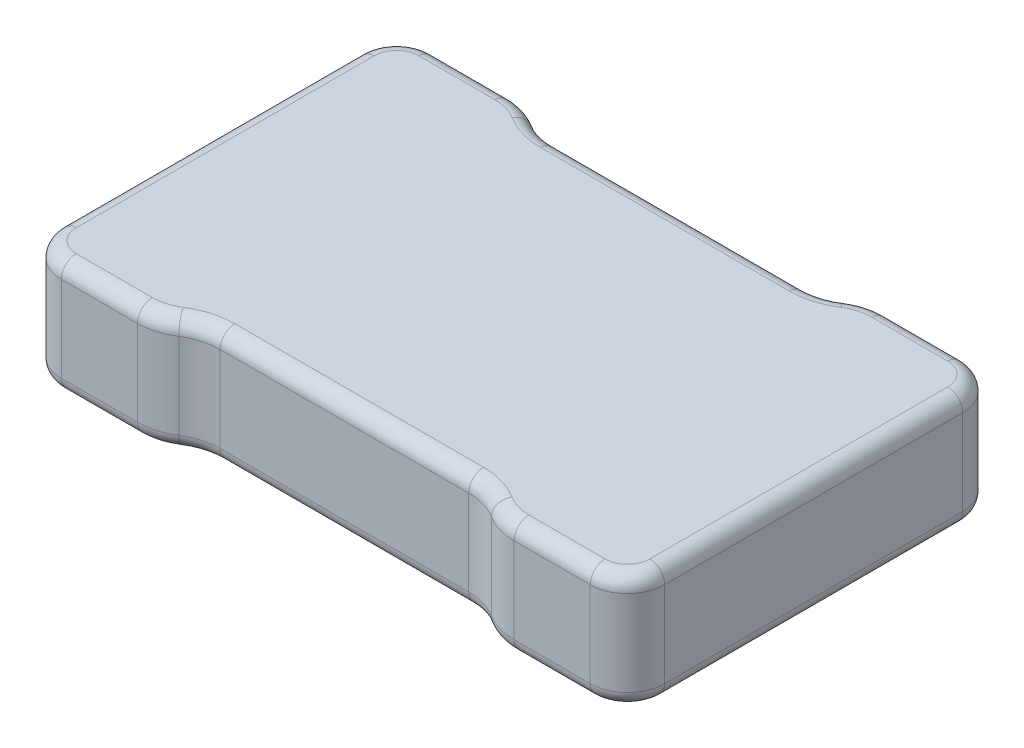
SolidWorks part; units mm, degrees
ref_plane "Front Plane" through (0, 0, 0) normal (0, 0, 1) x (1, 0, 0)
ref_plane "Top Plane" through (0, 0, 0) normal (0, 1, 0) x (1, 0, 0)
ref_plane "Right Plane" through (0, 0, 0) normal (1, 0, 0) x (0, 0, -1)
sketch "Sketch1" plane through (0, 0, 0) normal (0, 1, 0) x (1, 0, 0)
  line L0 (-55, 0) -> (55, 0) construction
  line L1 (-40.5, 25) -> (40.5, 25)
  line L2 (-40.5, 25) -> (-40.5, -25)
  line L3 (-40.5, -25) -> (40.5, -25)
  line L4 (40.5, 25) -> (40.5, -25)
  line L5 (0, -55) -> (0, 55) construction
  dimension "D1" = 25
  dimension "D2" = 50
  dimension "D3" = 81
  dimension "D4" = 40.5
extrude "Boss-Extrude1" add sketch "Sketch1" along normal blind 15.5
sketch "Sketch2" plane through (0, 15.5, 0) normal (0, 1, 0) x (1, 0, 0)
  line L0 (-40.5, 25) -> (-40.5, -25) construction
  line L1 (-40.5, 25) -> (-40.5, 22.5) construction
  line L2 (-40.5, 22.5) -> (-40.5, -22.5) construction
  line L3 (-40.5, -22.5) -> (-40.5, -25) construction
  line L4 (-40.5, 22.5) -> (40.5, 22.5) construction
  line L5 (40.5, -25) -> (40.5, 25) construction
  line L6 (-40.5, -22.5) -> (40.5, -22.5) construction
  line L7 (40.5, 22.5) -> (22.5, 22.5) construction
  line L8 (22.5, 22.5) -> (-22.5, 22.5) construction
  line L9 (-22.5, 22.5) -> (-40.5, 22.5) construction
  line L10 (-22.5, 22.5) -> (-22.5, -25) construction
  line L11 (-40.5, -25) -> (40.5, -25) construction
  line L12 (22.5, 22.5) -> (22.5, -25) construction
  line L13 (22.5, 25) -> (-22.5, 25)
  line L14 (40.5, 25) -> (-40.5, 25) construction
  line L15 (-22.5, 25) -> (-22.5, 22.5)
  line L16 (-22.5, 22.5) -> (22.5, 22.5)
  line L17 (22.5, 22.5) -> (22.5, 25)
  line L18 (-22.5, -25) -> (-22.5, -22.5)
  line L19 (-22.5, -22.5) -> (22.5, -22.5)
  line L20 (22.5, -22.5) -> (22.5, -25)
  line L21 (22.5, -25) -> (-22.5, -25)
  dimension "D1" = 2.5
  dimension "D2" = 2.5
  dimension "D3" = 18
  dimension "D4" = 18
extrude "Cut-Extrude1" cut sketch "Sketch2" against normal through all
fillet "Fillet1" radius 8 4 edges at (22.5, 7.75, 22.5) (-22.5, 7.75, 22.5) (-22.5, 7.75, -22.5) (22.5, 7.75, -22.5)
fillet "Fillet2" radius 8 4 edges at (22.5, 7.75, 25) (22.5, 7.75, -25) (-22.5, 7.75, -25) (-22.5, 7.75, 25)
fillet "Fillet3" radius 5 4 edges at (40.5, 7.75, -25) (40.5, 7.75, 25) (-40.5, 7.75, 25) (-40.5, 7.75, -25)
fillet "Fillet4" radius 2 40 edges at (-18.9266, 0, -22.8189) (-23.0422, 0, -24.6811) (-30.3892, 0, -25) (-39.0355, 0, -23.5355) (-40.5, 0, 0) (-39.0355, 0, 23.5355) (-30.3892, 0, 25) (-23.0422, 0, 24.6811) (-18.9266, 0, 22.8189) (0, 0, 22.5) (18.9266, 0, 22.8189) (23.0422, 0, 24.6811) (30.3892, 0, 25) (39.0355, 0, 23.5355) (40.5, 0, 0) (39.0355, 0, -23.5355) (30.3892, 0, -25) (23.0422, 0, -24.6811) (18.9266, 0, -22.8189) (-18.9266, 15.5, -22.8189) (-23.0422, 15.5, -24.6811) (-30.3892, 15.5, -25) (-39.0355, 15.5, -23.5355) (-40.5, 15.5, 0) (-39.0355, 15.5, 23.5355) (-30.3892, 15.5, 25) (-23.0422, 15.5, 24.6811) (-18.9266, 15.5, 22.8189) (0, 15.5, 22.5) (18.9266, 15.5, 22.8189) (23.0422, 15.5, 24.6811) (30.3892, 15.5, 25) (39.0355, 15.5, 23.5355) (40.5, 15.5, 0) (39.0355, 15.5, -23.5355) (30.3892, 15.5, -25) (23.0422, 15.5, -24.6811) (18.9266, 15.5, -22.8189) (0, 0, -22.5) (0, 15.5, -22.5)
